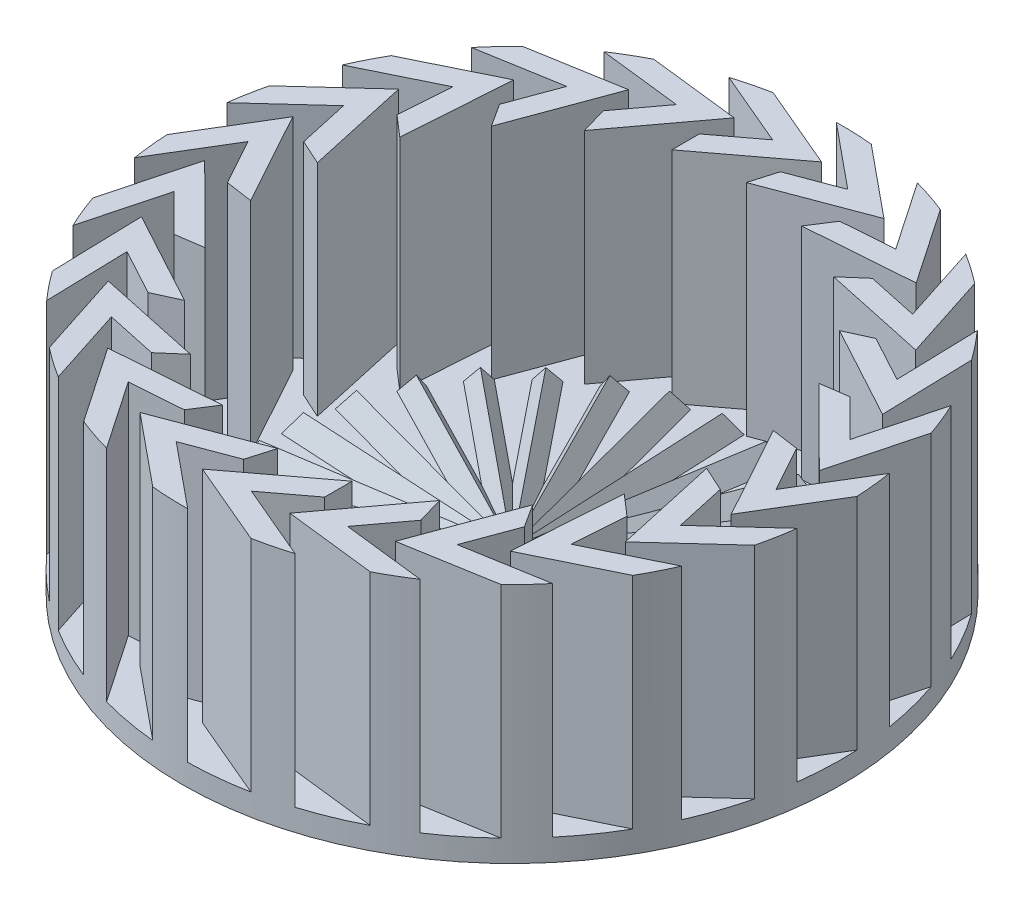
SolidWorks part; units mm, degrees
ref_plane "Front Plane" through (0, 0, 0) normal (0, 0, 1) x (1, 0, 0)
ref_plane "Top Plane" through (0, 0, 0) normal (0, 1, 0) x (1, 0, 0)
ref_plane "Right Plane" through (0, 0, 0) normal (1, 0, 0) x (0, 0, -1)
sketch "Sketch2" plane through (0, 0, 0) normal (0, 1, 0) x (1, 0, 0)
  circle A0 centre (0, 0) radius 30
  dimension "D1" = 60
extrude "Boss-Extrude1" add sketch "Sketch2" along normal blind 2
sketch "Sketch3" plane through (0, 2, 0) normal (0, 1, 0) x (1, 0, 0)
  line L0 (0, 0) -> (0, 30) construction
  line L1 (-7.364, 29.0821) -> (0, 25.9563) construction
  line L2 (0, 25.9563) -> (-6.3891, 21.1418) construction
  line L3 (-7.7548, 28.1616) -> (-1.9851, 25.7126) construction
  line L4 (-1.9851, 25.7126) -> (-6.9909, 21.9404) construction
  line L5 (-6.9733, 30.0026) -> (1.9851, 26.2) construction
  line L6 (1.9851, 26.2) -> (-5.7873, 20.3431) construction
  line L7 (-1.9851, 25.7126) -> (-8.9023, 28.6487)
  line L8 (1.9851, 26.2) -> (-5.686, 29.4562)
  line L11 (-5.7873, 20.3431) -> (1.9851, 26.2)
  line L12 (-1.9851, 25.7126) -> (-5.7873, 22.8474)
  line L13 (-5.7873, 22.8474) -> (-5.7873, 20.3431)
  circle A0 centre (0, 0) radius 30 construction
  arc A1 (-8.9023, 28.6487) -> (-5.686, 29.4562) centre (0, 0) cw
  dimension "D1" = 60
  dimension "D2" = 8
  dimension "D3" = 67
  dimension "D4" = 1
  dimension "D5" = 1
extrude "Boss-Extrude2" add sketch "Sketch3" along normal blind 20
pattern_circular "CirPattern1" count 22 over 360 about axis through (0, 2, 0) along (0, 1, 0) of "Boss-Extrude2"
sketch "Sketch5" plane through (0, 2, 0) normal (0, 1, 0) x (1, 0, 0)
  line L0 (0, 0) -> (11.5845, 17.6956) construction
  line L1 (0.8367, -0.5477) -> (12.4211, 17.1479)
  line L2 (-0.8367, 0.5477) -> (10.7478, 18.2434)
  line L3 (-0.8367, 0.5477) -> (0.8367, -0.5477)
  line L4 (10.7478, 18.2434) -> (12.4211, 17.1479)
  dimension "D1" = 1
  dimension "D2" = 1
extrude "Boss-Extrude4" add sketch "Sketch5" along normal blind 2 draft 30
pattern_circular "CirPattern2" count 30 over 360 about axis through (0, 2, 0) along (0, -1, 0) of "Boss-Extrude4" reverse direction yes
